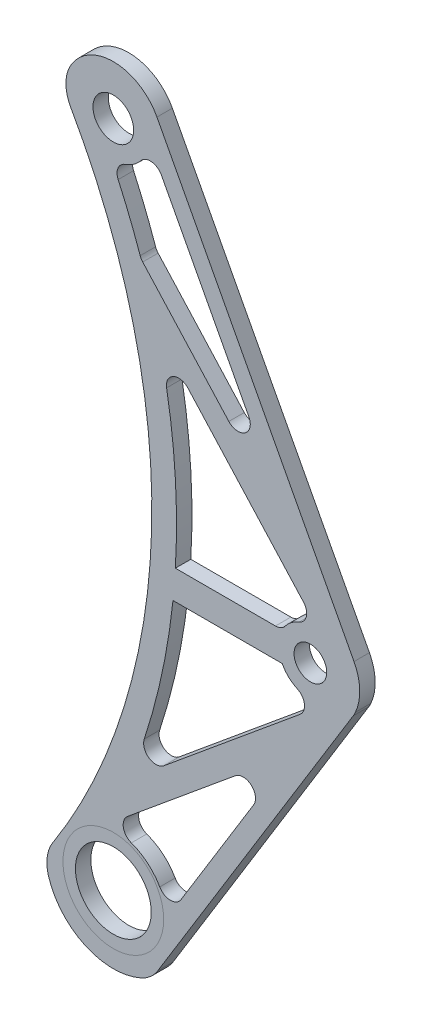
SolidWorks part; units mm, degrees
material "6061-T6 (SS)"
ref_plane "X-Y Datum" through (0, 0, 0) normal (0, 0, 1) x (1, 0, 0)
ref_plane "X-Z Datum" through (0, 0, 0) normal (0, 1, 0) x (1, 0, 0)
ref_plane "Y-Z Datum" through (0, 0, 0) normal (1, 0, 0) x (0, 0, -1)
sketch "Sketch1" plane through (0, 0, 0) normal (0, 0, 1) x (1, 0, 0)
  line L0 (0, 0) -> (0, 137.668) construction
  line L1 (0, 137.668) -> (40.5829, 60.8625) construction
  line L2 (40.5829, 60.8625) -> (0, 0) construction
  line L3 (-13.97, 0) -> (-10.16, 137.668)
  line L4 (8.9831, 142.4145) -> (49.566, 65.6091)
  line L5 (49.566, 56.116) -> (8.1778, -11.3263)
  circle A0 centre (0, 0) radius 7.8105
  circle A1 centre (40.5829, 60.8625) radius 3.3655
  circle A2 centre (0, 137.668) radius 4.191
  arc A3 (-10.16, 137.668) -> (8.9831, 142.4145) centre (0, 137.668) cw
  arc A4 (49.566, 65.6091) -> (49.566, 56.116) centre (40.5829, 60.8625) cw
  arc A5 (8.1778, -11.3263) -> (-13.97, 0) centre (0, 0) cw
  arc A6 (-10.16, 137.668) -> (-13.97, 0) centre (-120.8325, 71.8442) cw
  circle A7 centre (0, 0) radius 11.5718
  point P16 (50.7429, 60.8625)
  dimension "D4" = 15.621
  dimension "D5" = 6.731
  dimension "D6" = 8.382
  dimension "D7" = 13.97
  dimension "D8" = 10.16
  dimension "D9" = 10.16
  dimension "D1" = 137.668
  dimension "D2" = 86.868
  dimension "D3" = 73.152
  dimension "D11" = 125.83
extrude "Boss-Extrude1" add sketch "Sketch1" along normal blind 3.175 contours A3 A6 A5 L5 A4 L4 A2 A1 A0 | A6 A7 A0 region at (18.3815, 67.9714, 0) region at (-11.2445, 0, 0)
sketch "Sketch2" plane through (0, 0, 3.175) normal (0, 0, 1) x (1, 0, 0)
  line L0 (10.9735, 0.5136) -> (45.1141, 56.146)
  line L1 (49.566, 56.116) -> (8.1778, -11.3263) construction
  line L2 (45.4652, 65.2146) -> (7.3584, 137.334)
  line L3 (8.9831, 142.4145) -> (49.566, 65.6091) construction
  line L4 (34.771, 63.8625) -> (12.7772, 63.8625)
  line L5 (34.771, 57.8625) -> (12.2832, 57.8625)
  line L6 (42.7865, 67.0206) -> (9.0338, 104.248)
  line L7 (37.3415, 80.5892) -> (5.7001, 115.488)
  line L8 (45.1141, 56.146) -> (3.1725, 21.4652)
  line L9 (36.9014, 42.7633) -> (-1.6872, 10.8552)
  line L10 (40.5829, 60.8625) -> (-57.185, 60.8625)
  arc A4 (-0.4312, 130.3146) -> (-1.6872, 10.8552) centre (-120.8325, 71.8442) cw
  arc A5 (-13.97, 0) -> (-10.16, 137.668) centre (-120.8325, 71.8442) ccw construction
  circle A7 centre (0, 0) radius 10.9855
  circle A9 centre (40.5829, 60.8625) radius 6.5405
  circle A10 centre (0, 137.668) radius 7.366
  circle A11 centre (0, 137.668) radius 4.191 construction
  circle A12 centre (40.5829, 60.8625) radius 3.3655 construction
  circle A13 centre (0, 0) radius 7.8105 construction
  dimension "D3" = 3.175
  dimension "D1" = 3.175
  dimension "D2" = 3.175
  dimension "D6" = 5.08
  dimension "D4" = 3.81
  dimension "D5" = 3.81
  dimension "D7" = 5.08
  dimension "D8" = 5.08
  dimension "D9" = 3
  dimension "D10" = 3
extrude "Cut-Extrude1" cut sketch "Sketch2" against normal blind 6.35 contours A7 L0 L9 A4 | A9 A4 L8 | L6 A4 | A10 A4 L7 L2 region at (16.5204, 19.3286, 3.175) region at (20.5771, 45.529, 3.175) region at (15.0547, 113.2832, 3.175) region at (22.4636, 77.3864, 3.175)
fillet "Fillet1" radius 2.54 12 edges at (10.9735, 0.5136, 1.5875) (36.9014, 42.7633, 1.5875) (44.3643, 55.526, 1.5875) (3.1725, 21.4652, 1.5875) (9.0338, 104.248, 1.5875) (37.3415, 80.5892, 1.5875) (5.7001, 115.488, 1.5875) (-0.4312, 130.3146, 1.5875) (7.3584, 137.334, 1.5875) (-1.6872, 10.8552, 1.5875) (42.7865, 67.0206, 1.5875) (34.771, 63.8625, 1.5875)
sketch "Sketch3" [suppressed] plane through (0, 0, 4.7625) normal (0, 0, 1) x (1, 0, 0)
  line L1 (13.9694, 0.1347) -> (39.7508, 21.6818)
  line L2 (9.979, 66.6708) -> (39.902, 40.8139)
  line L3 (55.423, 60.7241) -> (9.3949, 172.5239) construction
  line L6 (12.9992, 5.1168) -> (35.8725, 24.2335)
  line L8 (8.1778, -11.3263) -> (55.423, 52.9883) construction
  arc A0 (39.902, 40.8139) -> (35.8725, 24.2335) centre (43.2483, 31.2208) ccw
  arc A1 (-1.655, 13.8716) -> (12.9992, 5.1168) centre (0, 0) cw
  arc A3 (0.9228, 58.462) -> (-1.655, 13.8716) centre (-31.1833, 37.9483) cw
  circle A4 centre (43.2483, 31.2208) radius 10.16
  circle A5 centre (0, 0) radius 13.97
  arc A6 (0.9228, 58.462) -> (9.979, 66.6708) centre (0, 68.58) ccw
  circle A7 centre (0, 68.58) radius 10.16
  arc A8 (-5.9452, 60.3411) -> (-7.4548, 11.8147) centre (-23.0858, 36.5876) cw
  arc A9 (-13.4408, 9.525) -> (-10.5128, 62.23) centre (-35.7711, 37.1994) ccw construction
  dimension "D1" = 10.16
  dimension "D2" = 10.16
  dimension "D3" = 13.97
  dimension "D6" = 6.7275
  dimension "D9" = 12.7
  dimension "D7" = 38.1
  dimension "D4" = 29.81
  dimension "D5" = 5.08
  dimension "D8" = 5.08
  dimension "D11" = 75.318
extrude "Cut-Extrude2" [suppressed] cut sketch "Sketch3" against normal blind 6.35 contours A6 A3 A1 L6 A0 L2 | A5 L1 A4 L6 | L6 A0 L2 A6 A3 A1
sketch3d "3DSketch1"
  line L0 (0, 137.668, 3.175) -> (0, 137.668, 0) construction
  line L1 (40.5829, 60.8625, 3.175) -> (40.5829, 60.8625, 0) construction
  point P0 (0, 137.668, 3.175)
  point P1 (40.5829, 60.8625, 3.175)
fillet "Fillet2" [suppressed] radius 6.35
fillet "Fillet4" [suppressed] radius 6.35
ref_axis "Axis1" through (0, 137.668, 3.175) along (0, 0, -1)
ref_axis "Axis2" through (40.5829, 60.8625, 3.175) along (0, 0, -1)
ref_plane "Plane1" through (23.5426, 4.1512, 0) normal (0.9848, 0.1736, 0) x (0, 0, -1)
ref_plane "Plane2" through (19.8415, -6.142, 0) normal (0.9553, -0.2957, 0) x (0, 0, -1)
sketch "Sketch4" plane through (23.5426, 4.1512, 0) normal (0.9848, 0.1736, 0) x (0, 0, -1)
  line L0 (-3.175, 166.0937) -> (-3.175, 170.2847)
sketch "Sketch5" plane through (19.8415, -6.142, 0) normal (0.9553, -0.2957, 0) x (0, 0, -1)
  line L0 (-3.175, 70.1413) -> (-3.175, 11.4039)
  line L1 (-0.3461, 48.6622) -> (-0.3461, 36.6839)
split line "Split Line1" [suppressed]
split line "Split Line2" [suppressed]
ref_point "Point2" [suppressed]
ref_axis "Axis3" through (0, 0, 3.175) along (0, 0, -1)
sketch "Sketch6" plane through (0, 0, 0) normal (0, 0, -1) x (-1, 0, 0)
  circle A0 centre (0, 0) radius 10.3708
split line "Split Line3"
fillet "Fillet5" radius 7.62 4 edges at (-13.97, 0, 1.5875) (-10.16, 137.668, 1.5875) (49.566, 56.116, 1.5875) (8.1778, -11.3263, 1.5875)
ref_point "Point4" [suppressed]
